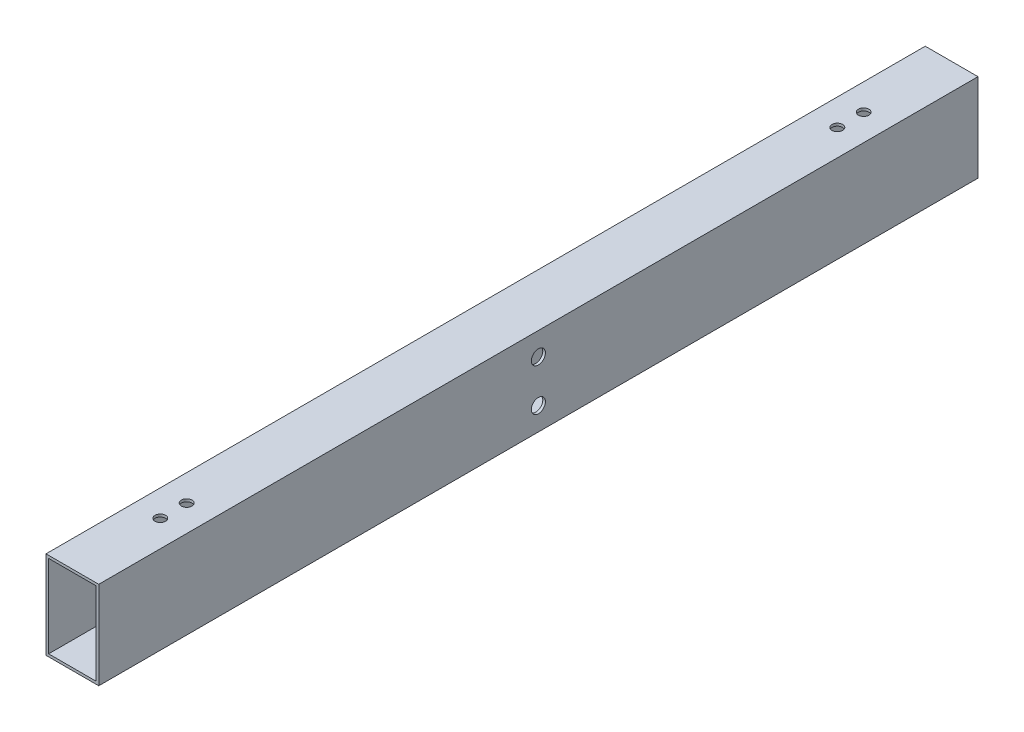
SolidWorks part; units mm, degrees
ref_plane "Płaszczyzna przednia" through (0, 0, 0) normal (0, 0, 1) x (1, 0, 0)
ref_plane "Płaszczyzna górna" through (0, 0, 0) normal (0, 1, 0) x (1, 0, 0)
ref_plane "Płaszczyzna prawa" through (0, 0, 0) normal (1, 0, 0) x (0, 0, -1)
sketch "Szkic1" plane through (0, 0, 0) normal (0, 0, 1) x (1, 0, 0)
  line L1 (0, 0) -> (30, 0)
  line L2 (0, 0) -> (0, 50)
  line L3 (0, 50) -> (30, 50)
  line L4 (30, 0) -> (30, 50)
  dimension "D1" = 50
  dimension "D2" = 30
sketch "Szkic2" plane through (0, 0, 0) normal (0, 0, 1) x (1, 0, 0)
  line L0 (30, 0) -> (30, 50) construction
  line L1 (1.5, 48.5) -> (28.5, 48.5)
  line L2 (1.5, 48.5) -> (1.5, 1.5)
  line L3 (1.5, 1.5) -> (28.5, 1.5)
  line L4 (28.5, 48.5) -> (28.5, 1.5)
  line L5 (0, 0) -> (0, 50) construction
  line L6 (0, 50) -> (30, 50) construction
  line L7 (0, 0) -> (30, 0) construction
  dimension "D1" = 1.5
  dimension "D2" = 1.5
  dimension "D3" = 1.5
  dimension "1,5" = 1.5
extrude "Dodanie-wyciągnięcie1" add sketch "Szkic1" along normal blind 500 contours L4 L3 L2 L1
extrude "Wytnij-wyciągnięcie7" cut sketch "Szkic2" along normal through all
sketch "Szkic5" plane through (0, 0, 0) normal (0, 1, 0) x (1, 0, 0)
  line L0 (0, -500) -> (0, 0) construction
  line L1 (0, -500) -> (30, -500) construction
  line L2 (0, 0) -> (30, 0) construction
  circle A0 centre (15, -450) radius 3
  circle A1 centre (15, -435) radius 3
  circle A2 centre (15, -50) radius 3
  circle A3 centre (15, -65) radius 3
  dimension "D1" = 6
  dimension "D2" = 15
  dimension "D3" = 50
  dimension "D4" = 6
  dimension "D5" = 15
  dimension "D6" = 15
  dimension "D7" = 6
  dimension "D8" = 15
  dimension "D9" = 50
  dimension "D10" = 6
  dimension "D11" = 15
  dimension "D12" = 15
extrude "Wytnij-wyciągnięcie13" cut sketch "Szkic5" along normal through all contours A3 | A2 | A1 | A0
sketch "Szkic6" plane through (30, 0, 0) normal (1, 0, 0) x (0, 0, -1)
  line L0 (-500, 25) -> (0, 25) construction
  line L1 (-500, 0) -> (-500, 50) construction
  line L2 (0, 0) -> (0, 50) construction
  line L3 (-250, 50) -> (-250, 0) construction
  line L4 (-500, 50) -> (0, 50) construction
  line L5 (16.5, 0) -> (-16.5, 0) construction
  circle A0 centre (-250, 37) radius 4
  circle A1 centre (-250, 13) radius 4
  point P16 (-250, 37)
  point P17 (-250, 37)
  dimension "D1" = 8
  dimension "D2" = 8
  dimension "D3" = 13
  dimension "D4" = 13
extrude "Wytnij-wyciągnięcie14" cut sketch "Szkic6" against normal through all
